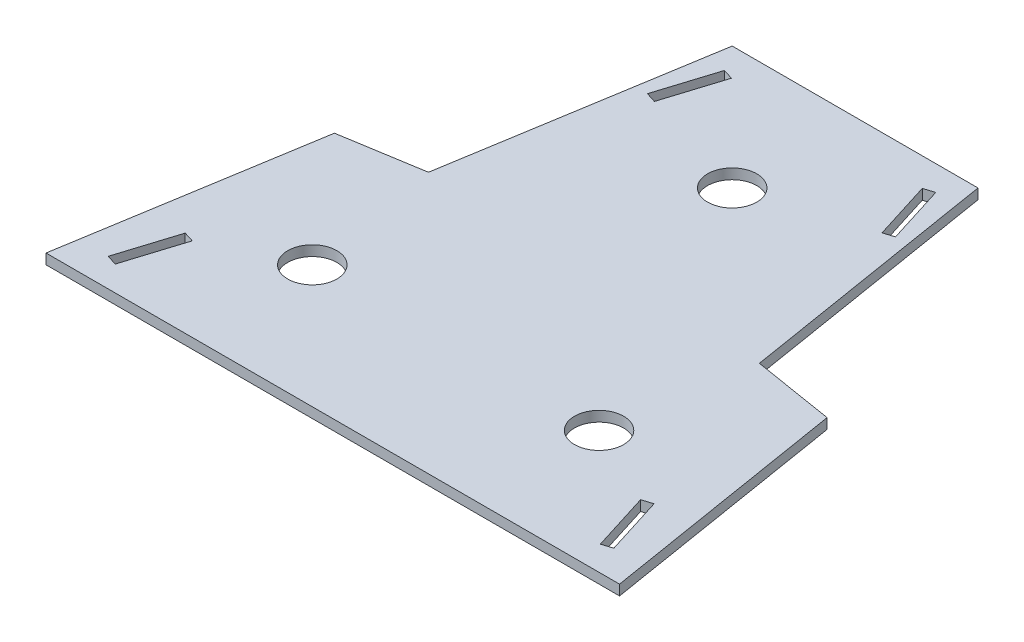
SolidWorks part; units mm, degrees
material "Acrylic (Medium-high impact)"
ref_plane "Front Plane" through (0, 0, 0) normal (0, 0, 1) x (1, 0, 0)
ref_plane "Top Plane" through (0, 0, 0) normal (0, 1, 0) x (1, 0, 0)
ref_plane "Right Plane" through (0, 0, 0) normal (1, 0, 0) x (0, 0, -1)
sketch "Sketch1" plane through (0, 0, 0) normal (0, 1, 0) x (1, 0, 0)
  line L0 (-140, 0) -> (140, 0)
  line L1 (140, 0) -> (120.264, 121.0641)
  line L2 (120.264, 121.0641) -> (80.7852, 127.5)
  line L3 (80.7852, 127.5) -> (60, 255)
  line L4 (-60, 255) -> (60, 255)
  line L6 (-60, 255) -> (-80.7852, 127.5)
  line L7 (-80.7852, 127.5) -> (-120.264, 121.0641)
  line L8 (-120.264, 121.0641) -> (-140, 0)
  line L9 (0, 0) -> (0, 255) construction
  circle A0 centre (0, 195) radius 12
  circle A1 centre (-70, 60) radius 12
  circle A2 centre (70, 60) radius 12
  dimension "D1" = 24
  dimension "D2" = 24
  dimension "D3" = 24
  dimension "D4" = 60
  dimension "D5" = 60
  dimension "D6" = 140
  dimension "D7" = 135
  dimension "D8" = 127.5
  dimension "D9" = 280
  dimension "D10" = 120
  dimension "D11" = 40
extrude "Boss-Extrude1" add sketch "Sketch1" along normal blind 5
sketch "Sketch2" plane through (0, 5, 0) normal (0, 1, 0) x (1, 0, 0)
  line L0 (0, 0) -> (0, 255) construction
  line L1 (60, 255) -> (-60, 255) construction
  line L2 (-125, 0) -> (-45, 255) construction
  line L3 (-60.564, 214.159) -> (-51.5838, 242.7833)
  line L4 (-140, 0) -> (140, 0) construction
  line L5 (-60.564, 214.159) -> (-55.5548, 212.5874)
  line L6 (-51.5838, 242.7833) -> (-46.5746, 241.2118)
  line L7 (-55.5548, 212.5874) -> (-46.5746, 241.2118)
  line L8 (-60.564, 214.159) -> (-46.5746, 241.2118) construction
  line L9 (-51.5838, 242.7833) -> (-55.5548, 212.5874) construction
  line L10 (109.436, 40.841) -> (123.4254, 13.7882) construction
  line L11 (-118.4162, 12.2167) -> (-109.436, 40.841)
  line L12 (-118.4162, 12.2167) -> (-123.4254, 13.7882)
  line L13 (-109.436, 40.841) -> (-114.4452, 42.4126)
  line L14 (-123.4254, 13.7882) -> (-114.4452, 42.4126)
  line L15 (-118.4162, 12.2167) -> (-114.4452, 42.4126) construction
  line L16 (-109.436, 40.841) -> (-123.4254, 13.7882) construction
  line L17 (118.4162, 12.2167) -> (114.4452, 42.4126) construction
  line L18 (51.5838, 242.7833) -> (55.5548, 212.5874) construction
  line L19 (60.564, 214.159) -> (46.5746, 241.2118) construction
  line L20 (125, 0) -> (45, 255) construction
  line L21 (123.4254, 13.7882) -> (114.4452, 42.4126)
  line L22 (109.436, 40.841) -> (114.4452, 42.4126)
  line L23 (118.4162, 12.2167) -> (123.4254, 13.7882)
  line L24 (118.4162, 12.2167) -> (109.436, 40.841)
  line L25 (55.5548, 212.5874) -> (46.5746, 241.2118)
  line L26 (51.5838, 242.7833) -> (46.5746, 241.2118)
  line L27 (60.564, 214.159) -> (55.5548, 212.5874)
  line L28 (60.564, 214.159) -> (51.5838, 242.7833)
  line L29 (-85, 127.5) -> (-163.8083, 152.2242) construction
  point P10 (-53.5693, 227.6854)
  point P13 (-116.4307, 27.3146)
  point P31 (116.4307, 27.3146)
  point P32 (53.5693, 227.6854)
  dimension "D1" = 15
  dimension "D2" = 15
  dimension "D3" = 5.25
  dimension "D4" = 30
  dimension "D5" = 180
extrude "Cut-Extrude1" cut sketch "Sketch2" against normal blind 5
